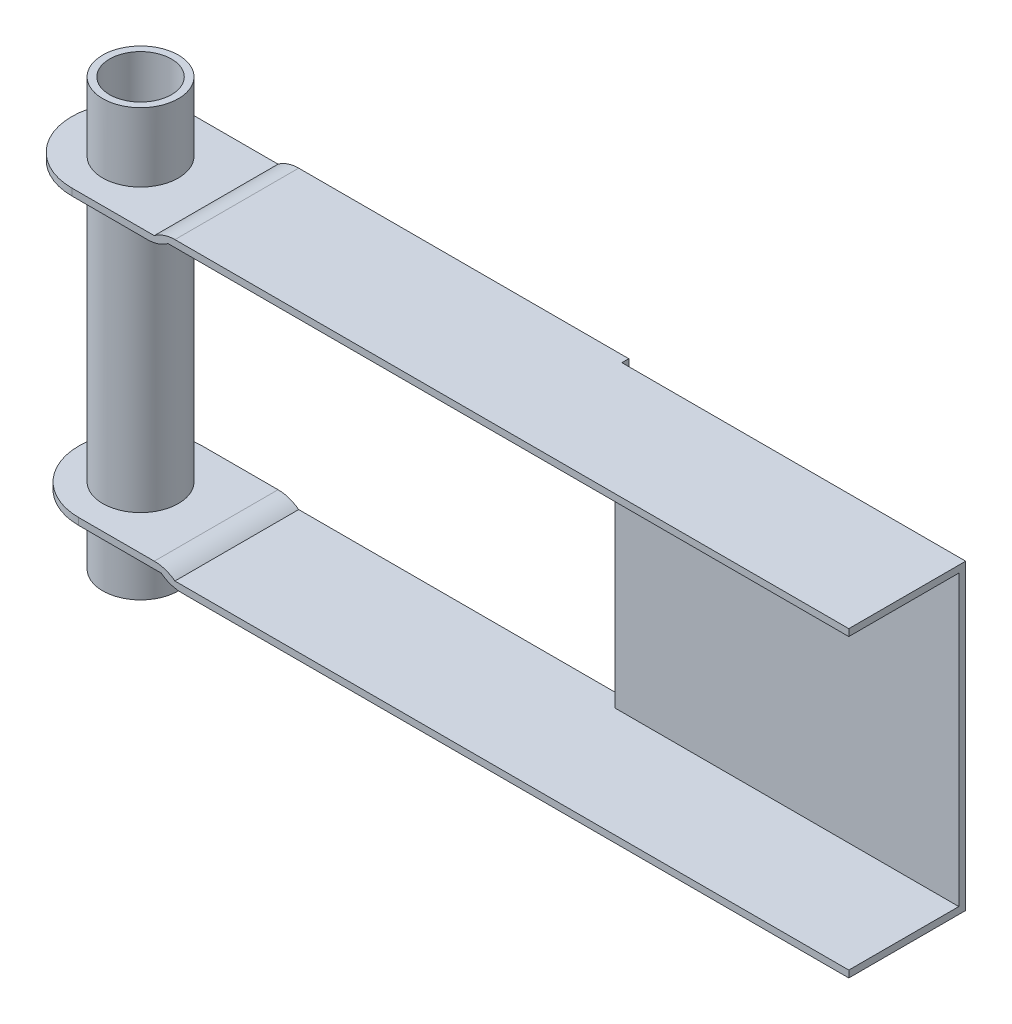
SolidWorks part; units mm, degrees
material "Aleación 1060"
ref_plane "Alzado" through (0, 0, 0) normal (0, 0, 1) x (1, 0, 0)
ref_plane "Planta" through (0, 0, 0) normal (0, 1, 0) x (1, 0, 0)
ref_plane "Vista lateral" through (0, 0, 0) normal (1, 0, 0) x (0, 0, -1)
sketch "Croquis1" plane through (0, 0, 0) normal (0, 0, 1) x (1, 0, 0)
  line L1 (0, 0) -> (50, 0)
  line L2 (0, 0) -> (0, -44)
  line L3 (0, -44) -> (50, -44)
  line L4 (50, 0) -> (50, -44)
  dimension "D1" = 44
  dimension "D2" = 50
extrude "Saliente-Extruir1" add sketch "Croquis1" along normal blind 1
sketch "Croquis2" plane through (0, 0, 1) normal (0, 0, 1) x (1, 0, 0)
  line L19 (50, -1) -> (0, -1)
  line L20 (50, -1) -> (0, -1)
  line L21 (0, -44) -> (0, -43)
  line L22 (0, -43) -> (50, -43)
  line L23 (0, -43) -> (50, -43)
  line L24 (50, -43) -> (50, -44)
  line L25 (50, -44) -> (0, -44)
  line L26 (0, -43) -> (50, -43)
  line L27 (0, -1) -> (0, 0)
  line L28 (0, 0) -> (50, 0)
  line L29 (50, 0) -> (50, -1)
  line L30 (50, -1) -> (0, -1)
  line M3 (0, 0) -> (0, -44)
  line M4 (0, -44) -> (50, -44)
  line M5 (50, -44) -> (50, 0)
  line M6 (50, 0) -> (0, 0)
  dimension "D1" = 1
  dimension "D2" = 1
extrude "Saliente-Extruir2" add sketch "Croquis2" along normal blind 16 contours L20 M5 M6 M3 | L23 M3 M4 M5 region at (25, -0.5, 1) region at (25, -43.5, 1)
sketch "Croquis3" plane through (0, 0, 0) normal (-1, 0, 0) x (0, 0, 1)
  line L0 (17, -44) -> (-1, -44)
  line L1 (17, -44) -> (17, -43)
  line L2 (17, -43) -> (-1, -43)
  line L3 (-1, -43) -> (-1, -44)
  line L4 (17, -1) -> (17, 0)
  line L5 (17, 0) -> (-1, 0)
  line L6 (17, 0) -> (17, -1)
  line L7 (17, -1) -> (-1, -1)
  line L8 (-1, -1) -> (-1, 0)
  line M1 (0, 0) -> (0, -44)
  line M2 (0, -44) -> (17, -44)
  line M3 (17, -44) -> (17, -43)
  line M4 (17, -43) -> (1, -43)
  line M6 (1, -1) -> (17, -1)
  line M7 (17, -1) -> (17, 0)
  line M8 (17, 0) -> (0, 0)
extrude "Saliente-Extruir3" add sketch "Croquis3" along normal blind 50 contours L2 M4 M1 M2 M3 | L2 L3 L0 M1 | L8 L7 L5 M1 | L7 M6 M7 M8 M1 region at (0, -0.5, -0.5) region at (0, -0.5, 8.5) region at (0, -43.5, 8.5) region at (0, -43.5, -0.5)
sketch "Croquis4" plane through (0, -1, 0) normal (0, -1, 0) x (1, 0, 0)
  line L0 (-50, -1) -> (-51, -1)
  line L1 (-51, -1) -> (-51, 17)
  line L2 (-51, 17) -> (-50, 17)
  line L3 (-50, -1) -> (-50, 17)
  line L10 (0, 1) -> (50, 1)
  line L11 (50, 1) -> (50, 17)
  line L12 (50, 17) -> (-50, 17)
  line L13 (-50, 17) -> (-50, -1)
  line L14 (-50, -1) -> (0, -1)
  line L15 (0, -1) -> (0, 0)
  line L16 (0, 0) -> (0, 1)
  line L17 (0, 1) -> (50, 1)
  line L18 (50, 1) -> (50, 17)
  line L19 (50, 17) -> (-50, 17)
  line L21 (-50, -1) -> (0, -1)
  line L22 (0, -1) -> (0, 0)
  line L23 (0, 0) -> (0, 1)
  line M12 (-50, 17) -> (-50, -1)
  dimension "D1" = 1
  dimension "D2" = 0
extrude "Saliente-Extruir4" add sketch "Croquis4" along normal blind 1 separate body contours L2 L1 L0 M12 region at (-50.5, -1, 8)
sketch "Croquis6" plane through (0, -1, 0) normal (0, 1, 0) x (1, 0, 0)
  line L0 (-51, 1) -> (-51, -17)
  line L1 (-51, -17) -> (-50, -17)
  line L2 (-50, -17) -> (-50, 1)
  line L3 (-50, 1) -> (-51, 1)
extrude "Saliente-Extruir5" add sketch "Croquis6" along normal blind 1
sketch "Croquis7" plane through (-51, 0, 0) normal (-1, 0, 0) x (0, 0, 1)
  line L0 (17, -2) -> (17, -1)
  line L1 (17, 0) -> (17, -2) construction
  line L2 (17, -1) -> (-1, -1)
  line L3 (-1, 0) -> (-1, -2) construction
  line L4 (-1, -1) -> (-1, -2)
  line L5 (-1, -2) -> (17, -2)
sketch "Croquis12" plane through (0, -43, 0) normal (0, 1, 0) x (1, 0, 0)
  line L0 (-50, 1) -> (-50, -17)
  line L1 (-50, -17) -> (-49, -17)
  line L2 (-50, -17) -> (50, -17) construction
  line L3 (-49, -17) -> (-49, 1)
  line L4 (-50, 1) -> (0, 1) construction
  line L5 (-49, 1) -> (-50, 1)
extrude "Saliente-Extruir11" add sketch "Croquis12" along normal blind 1
sketch "Croquis13" plane through (-50, 0, 0) normal (-1, 0, 0) x (0, 0, 1)
  line L0 (17, -42) -> (17, -43)
  line L1 (17, -44) -> (17, -42) construction
  line L2 (17, -43) -> (-1, -43)
  line L3 (-1, -42) -> (-1, -44) construction
  line L4 (-1, -43) -> (-1, -42)
  line L5 (-1, -42) -> (17, -42)
extrude "Saliente-Extruir12" add sketch "Croquis13" along normal blind 21
sketch "Croquis14" plane through (-51, 0, 0) normal (-1, 0, 0) x (0, 0, 1)
  line L0 (17, -1) -> (17, -2)
  line L1 (17, -2) -> (-1, -2)
  line L2 (-1, -2) -> (-1, -1)
  line L3 (-1, -1) -> (17, -1)
extrude "Saliente-Extruir13" add sketch "Croquis14" along normal blind 21
fillet "Redondeo4" radius 9 2 edges at (-72, -1.5, -1) (-72, -1.5, 17)
fillet "Redondeo5" radius 9 2 edges at (-71, -42.5, -1) (-71, -42.5, 17)
sketch "Croquis15" plane through (-49, 0, 0) normal (1, 0, 0) x (0, 0, -1)
  line L0 (-17, -42) -> (-17, -43) construction
  line L1 (1, -42) -> (-17, -42)
  line L2 (1, -42) -> (1, -43)
  line L3 (1, -43) -> (-17, -43)
  line L4 (-17, -42) -> (-17, -43)
  line L5 (-17, -43) -> (1, -43) construction
extrude "Saliente-Extruir14" add sketch "Croquis15" along normal blind 1
sketch "Croquis16" plane through (-50, 0, 0) normal (1, 0, 0) x (0, 0, -1)
  line L1 (1, -2) -> (-17, -2)
  line L2 (1, -2) -> (1, -1)
  line L3 (1, -1) -> (-17, -1)
  line L4 (-17, -2) -> (-17, -1)
extrude "Saliente-Extruir15" add sketch "Croquis16" along normal blind 1
fillet "Redondeo6" radius 5 2 edges at (-48, -42, 8) (-49, -2, 8)
fillet "Redondeo7" radius 5 2 edges at (-50, -44, 8) (-51, 0, 8)
sketch "Croquis17" plane through (0, -43, 0) normal (0, -1, 0) x (1, 0, 0)
  circle A0 centre (-62, 8) radius 5.5
  dimension "D1" = 11
extrude "Saliente-Extruir22" add sketch "Croquis17" along normal blind 10 and the other way blind 54
sketch "Croquis25" plane through (0, 11, 0) normal (0, 1, 0) x (1, 0, 0)
  circle A0 centre (-62, -8) radius 5.5
extrude "Cortar-Extruir5" cut sketch "Croquis25" against normal blind 2
sketch "Croquis26" plane through (0, 9, 0) normal (0, 1, 0) x (1, 0, 0)
  circle A0 centre (-62, -8) radius 5.5
  circle A2 centre (-62, -8) radius 4.641
  circle A3 centre (-62, -8) radius 4.5
  circle A4 centre (-62, -8) radius 4.5
  dimension "D1" = 1
extrude "Cortar-Extruir6" cut sketch "Croquis26" against normal through all contours A4 region at (-62, 9, 8)
